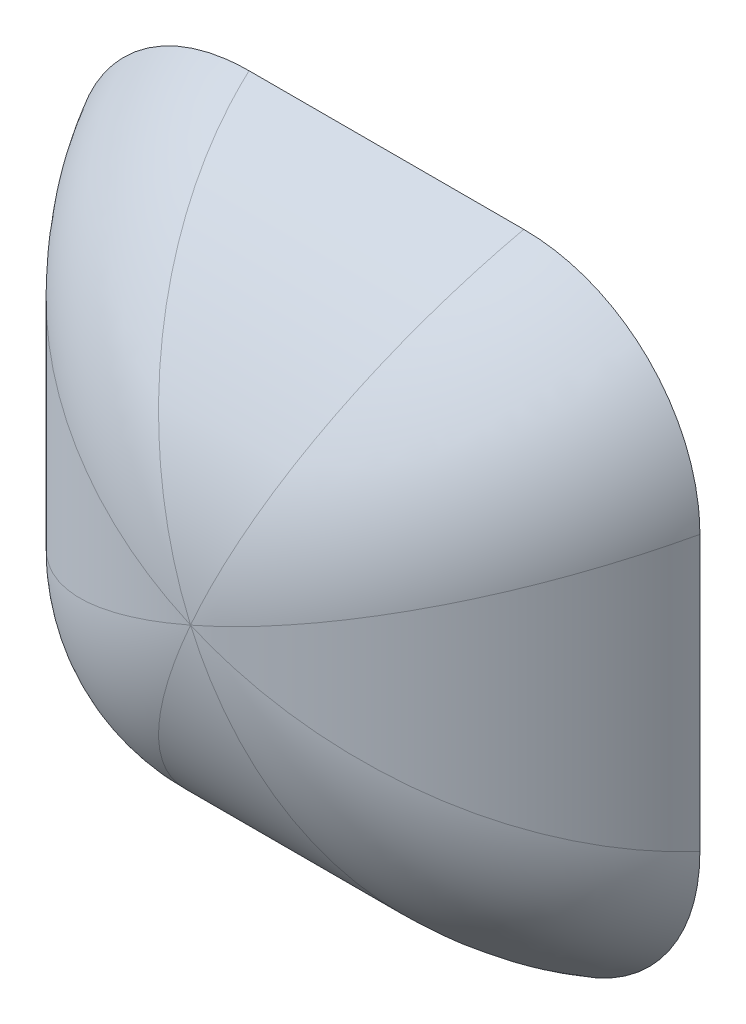
SolidWorks part; units mm, degrees
ref_plane "Płaszczyzna przednia" through (0, 0, 0) normal (0, 0, 1) x (1, 0, 0)
ref_plane "Płaszczyzna górna" through (0, 0, 0) normal (0, 1, 0) x (1, 0, 0)
ref_plane "Płaszczyzna prawa" through (0, 0, 0) normal (1, 0, 0) x (0, 0, -1)
sketch "Szkic1" plane through (0, 0, 0) normal (0, 0, 1) x (1, 0, 0)
  line L1 (0, 0) -> (32, 0)
  line L2 (0, 0) -> (0, 32)
  line L3 (0, 32) -> (32, 32)
  line L4 (32, 0) -> (32, 32)
  dimension "D1" = 32
extrude "Dodanie-wyciągnięcie1" add sketch "Szkic1" along normal blind 10
sketch "Szkic2" plane through (0, 32, 0) normal (0, 1, 0) x (1, 0, 0)
  line L0 (32, -10) -> (0, -10) construction
  line L1 (0, 0) -> (0, -10)
  line L2 (0, -10) -> (32, -10)
  line L3 (32, -10) -> (32, 0)
  arc A0 (0, 0) -> (32, 0) centre (16, 7.8) ccw
  point P0 (16, -10)
  line M2 (0, 0) -> (0, -10)
  line M3 (0, -10) -> (32, -10)
  line M4 (32, -10) -> (32, 0)
sketch "Szkic5" plane through (0, 0, 0) normal (-1, 0, 0) x (0, 0, 1)
  line L0 (10, 32) -> (10, 0) construction
  line L1 (0, 32) -> (10, 32)
  line L2 (10, 32) -> (0, 32) construction
  line L3 (10, 32) -> (10, 0)
  line L4 (10, 0) -> (0, 0)
  arc A0 (0, 32) -> (0, 0) centre (-7.8, 16) cw
  point P7 (10, 32)
  line M2 (0, 0) -> (10, 0)
  line M3 (10, 0) -> (10, 32)
  line M4 (10, 32) -> (0, 32)
extrude "Wytnij-wyciągnięcie2" cut sketch "Szkic5" against normal through all contours A0 L3 M4 | A0 M3 M2 region at (0, 3.7422, 7.2323) region at (0, 28.2578, 7.2323)
extrude "Wytnij-wyciągnięcie3" cut sketch "Szkic2" against normal through all contours A0 M2 M3 | A0 L2 M4 region at (3.7422, 32, 7.2323) region at (28.2578, 32, 7.2323)
ref_plane "Płaszczyzna2" through (16, 16, 10) normal (0.7071, 0.7071, 0) x (0.7071, -0.7071, 0)
fillet "Zaokrąglenie4" radius 10 2 edges at (6.566, 6.566, 7.2944) (25.434, 25.434, 7.2944)
fillet "Zaokrąglenie5" radius 10 2 edges at (6.566, 25.434, 7.2944) (25.434, 6.566, 7.2944)
sketch "Szkic6" plane through (0, 0, 0) normal (0, 0, -1) x (-1, 0, 0)
  line L0 (0, 23.0112) -> (0, 8.9888) construction
  line L5 (-23.0112, 32) -> (-8.9888, 32) construction
  line L6 (0, 23.0112) -> (0, 8.9888)
  line L7 (-23.0112, 32) -> (-8.9888, 32)
  spline S2 degree 3 poles (1053.2324, -232.9751) (-3147.8756, -780.4008) (26.1605, -114.5781) (-0.2176, 25.0578) (-0.2859, 25.344) (-0.4512, 25.9118) (-0.5487, 26.1944) (-0.8792, 27.0167) (-1.1508, 27.5366) (-1.7971, 28.5195) (-2.1762, 28.9855) (-3.0076, 29.8178) (-3.4622, 30.1894) (-4.2037, 30.6791) (-4.461, 30.8308) (-4.9838, 31.1048) (-5.5178, 31.3512) (-6.0734, 31.544) (-6.6399, 31.7099) (-6.9298, 31.7797) (-85.6915, 46.7426) (-276.5161, -963.9265) (80.0669, 3022.1656) knots -30.061427 -30.061427 -30.061427 -30.061427 0.125 0.125 0.1875 0.1875 0.25 0.25 0.375 0.375 0.5 0.5 0.625 0.625 0.6875 0.6875 0.75 0.8125 0.8125 0.875 0.875 17.698846 17.698846 17.698846 17.698846 only from (0, 23.0112) to (-8.9888, 32) construction
  spline S3 degree 3 poles (0, 23.0112) (0, 23.6062) (-0.0541, 24.1923) (-0.2176, 25.0578) (-0.2859, 25.344) (-0.4512, 25.9118) (-0.5487, 26.1944) (-0.8792, 27.0167) (-1.1508, 27.5366) (-1.7971, 28.5195) (-2.1762, 28.9855) (-3.0076, 29.8178) (-3.4622, 30.1894) (-4.2037, 30.6791) (-4.461, 30.8308) (-4.9838, 31.1048) (-5.5178, 31.3512) (-6.0734, 31.544) (-6.6399, 31.7099) (-6.9298, 31.7797) (-7.8044, 31.9459) (-8.3936, 32) (-8.9888, 32) knots 0 0 0 0 0.125 0.125 0.1875 0.1875 0.25 0.25 0.375 0.375 0.5 0.5 0.625 0.625 0.6875 0.6875 0.75 0.8125 0.8125 0.875 0.875 1 1 1 1
sketch "Szkic7" plane through (0, 0, 0) normal (0, 0, -1) x (-1, 0, 0)
  line L0 (0, 16) -> (-32, 16) construction
  line L10 (-21, 21) -> (-11, 21)
  line L11 (0, 23.0112) -> (0, 8.9888) construction
  line L12 (-32, 8.9888) -> (-32, 23.0112) construction
  line L13 (-16, 32) -> (-16, 0) construction
  line L14 (-23.0112, 32) -> (-8.9888, 32) construction
  line L15 (-8.9888, 0) -> (-23.0112, 0) construction
  line L16 (-21, 21) -> (-21, 11)
  line L17 (-21, 11) -> (-11, 11)
  line L18 (-11, 21) -> (-11, 11)
  line L19 (-21, 21) -> (-11, 11) construction
  line L20 (-21, 11) -> (-11, 21) construction
  point P0 (-16, 16)
  point P1 (-16, 16)
  dimension "D1" = 10
extrude "Dodanie-wyciągnięcie2" add sketch "Szkic7" along normal blind 8
